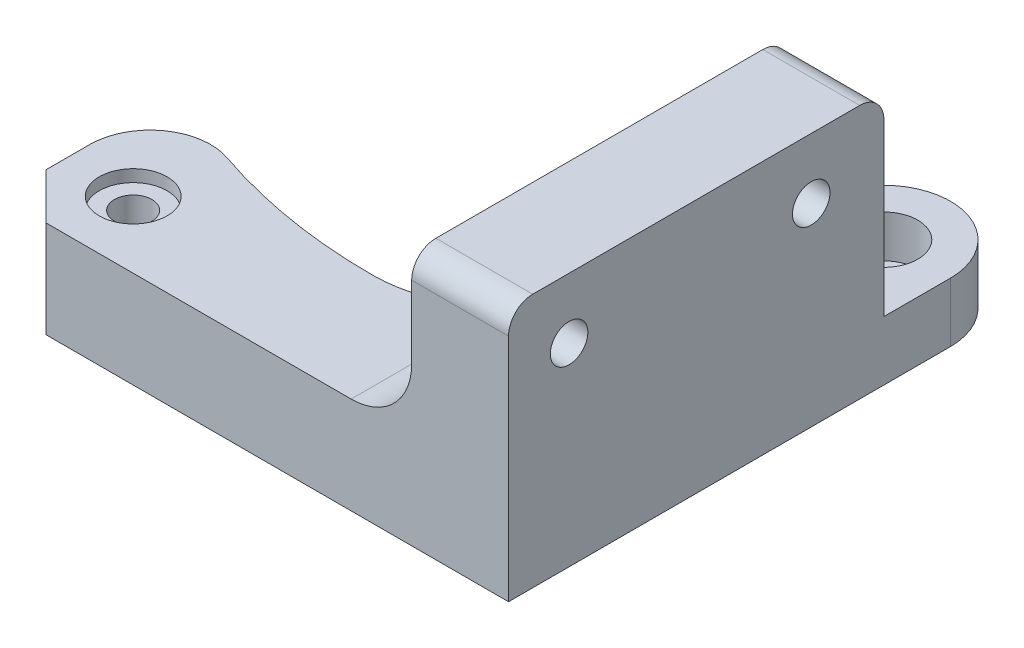
SolidWorks part; units mm, degrees
ref_plane "Alzado" through (0, 0, 0) normal (0, 0, 1) x (1, 0, 0)
ref_plane "Planta" through (0, 0, 0) normal (0, 1, 0) x (1, 0, 0)
ref_plane "Vista lateral" through (0, 0, 0) normal (1, 0, 0) x (0, 0, -1)
sketch "Croquis1" plane through (0, 0, 0) normal (0, 1, 0) x (1, 0, 0)
  line L0 (21, 42) -> (21, 0) construction
  line L1 (0, 0) -> (42, 0)
  line L2 (0, 0) -> (0, 42) construction
  line L3 (0, 42) -> (42, 42) construction
  line L4 (42, 0) -> (42, 36.5)
  line L5 (0, 15.0394) -> (0, 0)
  circle A0 centre (36.5, 36.5) radius 1.55
  circle A1 centre (5.5, 5.5) radius 1.55
  arc A2 (21, 9.75) -> (21, 32.25) centre (21, 21) ccw
  arc A3 (0, 15.0394) -> (21, 9.75) centre (20.9082, 53.7172) ccw
  arc A4 (42, 36.5) -> (31.1961, 37.9557) centre (36.5, 36.5) ccw
  arc A5 (21, 32.25) -> (31.1961, 37.9557) centre (20.567, 44.987) ccw
  dimension "D3" = 3.1
  dimension "D4" = 5.5
  dimension "D8" = 22.5
  dimension "D1" = 42
  dimension "D2" = 42
  dimension "D5" = 5.5
  dimension "D6" = 5.5
  dimension "D7" = 5.5
extrude "Saliente-Extruir2" add sketch "Croquis1" along normal blind 8
fillet "Redondeo1" radius 8 1 edges at (21, 4, -32.25)
fillet "Redondeo2" radius 5 1 edges at (0, 4, -15.0394)
sketch "Croquis2" plane through (0, 8, 0) normal (0, 1, 0) x (1, 0, 0)
  circle A0 centre (36.5, 36.5) radius 2.8
  circle A1 centre (5.5, 5.5) radius 2.8
  dimension "D1" = 5.6
extrude "Cortar-Extruir1" cut sketch "Croquis2" against normal blind 1
sketch "Croquis3" plane through (0, 8, 0) normal (0, 1, 0) x (1, 0, 0)
  line L1 (42, 0) -> (34, 0)
  line L2 (42, 0) -> (42, 31)
  line L3 (42, 31) -> (34, 31)
  line L4 (34, 0) -> (34, 31)
  dimension "D1" = 8
  dimension "D2" = 31
extrude "Saliente-Extruir3" add sketch "Croquis3" along normal blind 13
sketch "Croquis4" plane through (34, 0, 0) normal (-1, 0, 0) x (0, 0, 1)
  line L0 (-31, 8) -> (0, 8) construction
  line L2 (0, 21) -> (0, 8) construction
  circle A0 centre (-25, 16) radius 1.55
  circle A1 centre (-5, 16) radius 1.55
  dimension "D1" = 3.1
  dimension "D3" = 5
  dimension "D2" = 20
  dimension "D4" = 8
extrude "Cortar-Extruir2" cut sketch "Croquis4" against normal up to surface (8 mm away) up to face at (42, 9.6667, -22.5)
sketch "Croquis5" plane through (34, 0, 0) normal (-1, 0, 0) x (0, 0, 1)
  line L1 (-22.1, 17.6743) -> (-25, 19.3486)
  line L2 (-25, 19.3486) -> (-27.9, 17.6743)
  line L3 (-27.9, 17.6743) -> (-27.9, 14.3257)
  line L4 (-27.9, 14.3257) -> (-25, 12.6514)
  line L5 (-25, 12.6514) -> (-22.1, 14.3257)
  line L6 (-22.1, 14.3257) -> (-22.1, 17.6743)
  line L7 (-5, 19.3486) -> (-7.9, 17.6743)
  line L8 (-7.9, 17.6743) -> (-7.9, 14.3257)
  line L9 (-7.9, 14.3257) -> (-5, 12.6514)
  line L10 (-5, 12.6514) -> (-2.1, 14.3257)
  line L11 (-2.1, 14.3257) -> (-2.1, 17.6743)
  line L12 (-2.1, 17.6743) -> (-5, 19.3486)
  line L13 (-31, 21) -> (-31, 8) construction
  line L14 (0, 21) -> (0, 8) construction
  circle A0 centre (-25, 16) radius 2.9 construction
  circle A1 centre (-5, 16) radius 2.9 construction
  point P10 (-3.55, 13.4885)
  dimension "D1" = 5.8
  dimension "D2" = 5.8
extrude "Cortar-Extruir3" cut sketch "Croquis5" against normal blind 2.5 contours L1 L2 L3 L4 L5 L6 | L7 L8 L9 L10 L11 L12
fillet "Redondeo3" radius 5 1 edges at (34, 8, -15.5)
chamfer "Chaflán1" distance 3.8 angle 45 1 edges at (0, 4, 0)
fillet "Redondeo4" radius 2 2 edges at (38, 21, 0) (38, 21, -31)
sketch "Croquis6" plane through (0, 8, 0) normal (0, 1, 0) x (1, 0, 0)
  line L3 (29, 30.1408) -> (29, 31)
  line L4 (29, 31) -> (42, 31)
  line L5 (42, 31) -> (42, 36.5)
  line L6 (29, 30.1408) -> (29, 31)
  line L7 (29, 31) -> (42, 31)
  line L8 (42, 31) -> (42, 36.5)
  arc A3 (30.5227, 37.0307) -> (29, 30.1408) centre (36.7722, 32.0363) ccw
  arc A4 (42, 36.5) -> (31.1961, 37.9557) centre (36.5, 36.5) ccw
  arc A5 (30.5227, 37.0307) -> (31.1961, 37.9557) centre (20.567, 44.987) ccw
  arc A6 (30.5227, 37.0307) -> (29, 30.1408) centre (36.7722, 32.0363) ccw
  arc A7 (42, 36.5) -> (31.1961, 37.9557) centre (36.5, 36.5) ccw
  arc A8 (30.5227, 37.0307) -> (31.1961, 37.9557) centre (20.567, 44.987) ccw
  dimension "D1" = 0
extrude "Cortar-Extruir4" cut sketch "Croquis6" against normal blind 3.1
sketch "Croquis7" plane through (0, 4.9, 0) normal (0, 1, 0) x (1, 0, 0)
  circle A0 centre (36.5, 36.5) radius 2.8
  dimension "D1" = 5.6
extrude "Cortar-Extruir5" cut sketch "Croquis7" against normal blind 3.5
